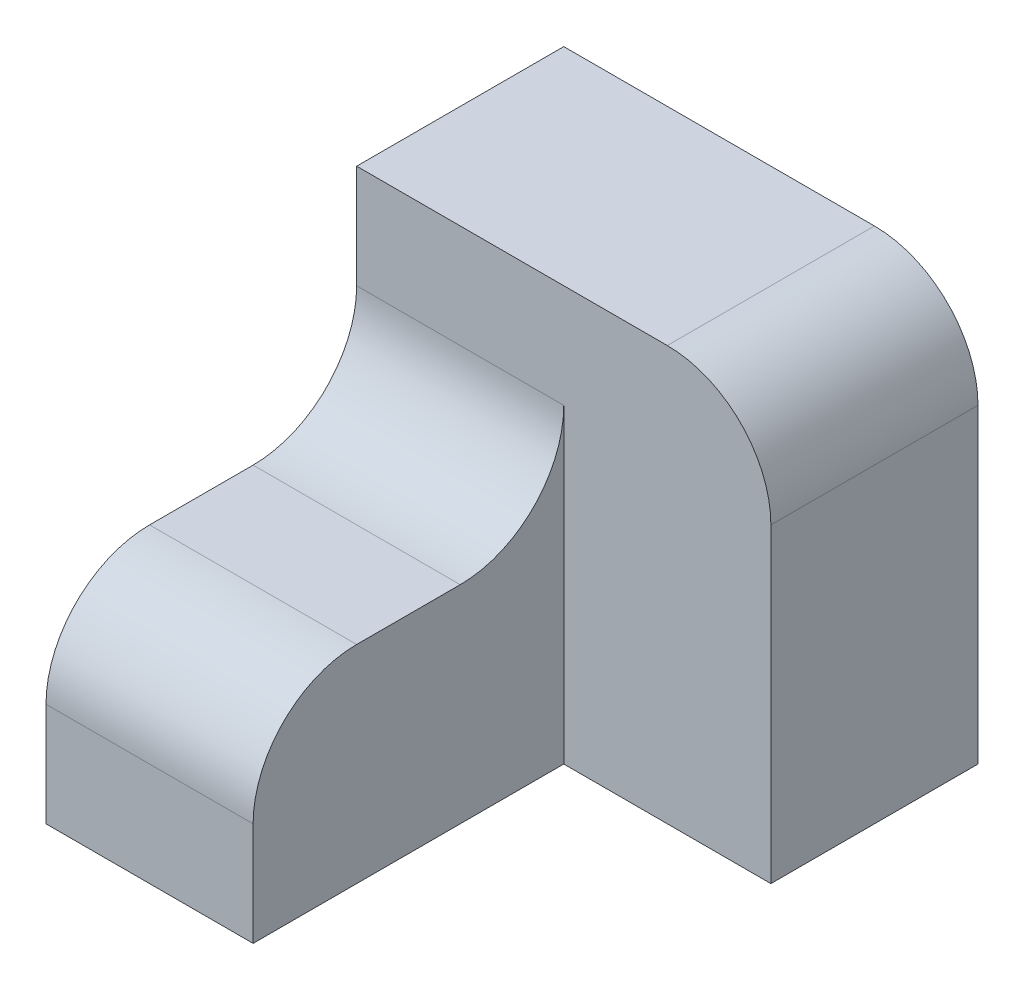
SolidWorks part; units mm, degrees
ref_plane "Front Plane" through (0, 0, 0) normal (0, 0, 1) x (1, 0, 0)
ref_plane "Top Plane" through (0, 0, 0) normal (0, 1, 0) x (1, 0, 0)
ref_plane "Right Plane" through (0, 0, 0) normal (1, 0, 0) x (0, 0, -1)
sketch "Sketch1" plane through (0, 0, 0) normal (0, 0, 1) x (1, 0, 0)
  line L1 (-30, -20) -> (-10, -20)
  line L2 (-10, -20) -> (-10, 0)
  line L3 (-10, 0) -> (-30, 0)
  line L4 (-30, 0) -> (-30, -20)
  dimension "D1" = 20
  dimension "Width" = 20
extrude "Boss-Extrude1" add sketch "Sketch1" along normal blind 30
sketch "Sketch2" plane through (0, 0, 0) normal (0, 0, 1) x (1, 0, 0)
  line L1 (-30, -20) -> (10, -20)
  line L2 (10, -20) -> (10, 20)
  line L3 (10, 20) -> (-30, 20)
  line L4 (-30, 20) -> (-30, -20)
  dimension "D1" = 40
  dimension "Width" = 40
extrude "Boss-Extrude2" add sketch "Sketch2" against normal blind 20
fillet "Fillet1" radius 10 3 edges at (-20, 0, 0) (10, 20, -10) (-20, 0, 30)
